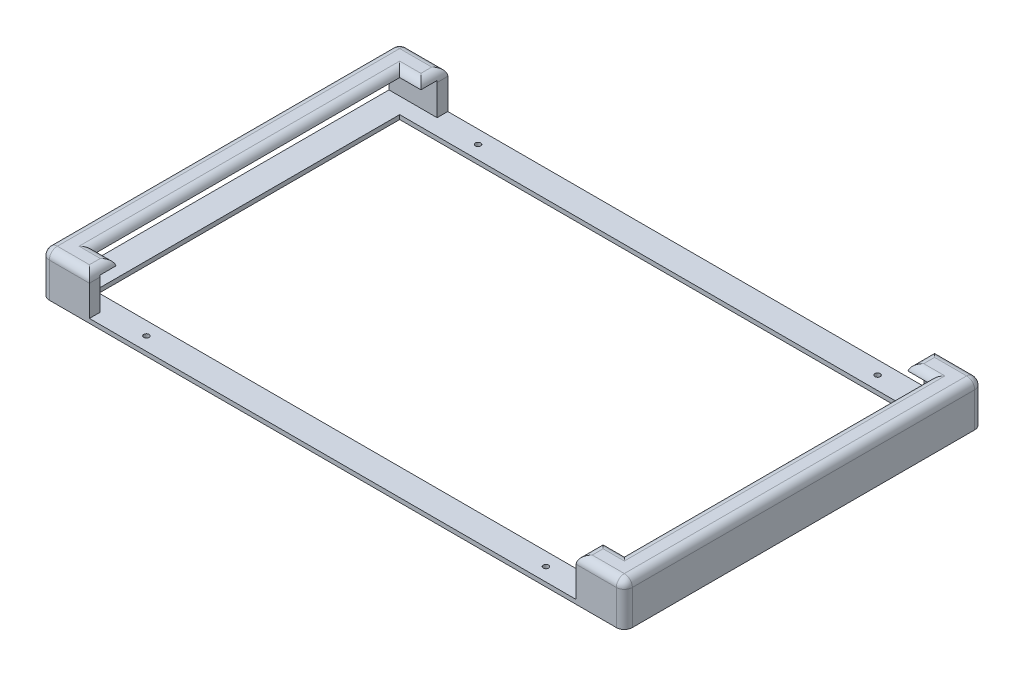
SolidWorks part; units mm, degrees
ref_plane "Спереди" through (0, 0, 0) normal (0, 0, 1) x (1, 0, 0)
ref_plane "Сверху" through (0, 0, 0) normal (0, 1, 0) x (1, 0, 0)
ref_plane "Справа" through (0, 0, 0) normal (1, 0, 0) x (0, 0, -1)
other "Configuration Table"
sketch "Основа" plane through (0, 0, 0) normal (0, 1, 0) x (1, 0, 0)
  line L1 (-109, -67) -> (109, -67)
  line L2 (-109, -67) -> (-109, 67)
  line L3 (-109, 67) -> (109, 67)
  line L4 (109, -67) -> (109, 67)
  line L5 (-109, -67) -> (109, 67) construction
  line L6 (-109, 67) -> (109, -67) construction
  line L7 (-99, -57) -> (99, -57)
  line L8 (-99, -57) -> (-99, 57)
  line L9 (-99, 57) -> (99, 57)
  line L10 (99, -57) -> (99, 57)
  line L11 (0, 57) -> (0, -57) construction
  line L12 (-99, 0) -> (99, 0) construction
  point P0 (0, 0)
  point P6 (0, 0)
  dimension "D1" = 134
  dimension "D2" = 218
  dimension "D3" = 114
  dimension "D4" = 198
extrude "Бобышка-Вытянуть2" add sketch "Основа" along normal blind 16
sketch "Эскиз2" plane through (-109, 0, 0) normal (-1, 0, 0) x (0, 0, 1)
  line L0 (0, 0) -> (0, 17.044) construction
  line L1 (63, 1.6) -> (-63, 1.6)
  line L2 (-63, 1.6) -> (-63, 13.6)
  line L3 (-63, 13.6) -> (63, 13.6)
  line L4 (-67, 0) -> (67, 0) construction
  line L5 (63, 1.6) -> (63, 13.6)
  point P10 (0, 13.6)
  point P11 (0, 1.6)
  dimension "D1" = 63
  dimension "D2" = 1.6
  dimension "D3" = 12
extrude "Вырез-Вытянуть1" cut sketch "Эскиз2" against normal blind 212
sketch "Эскиз3" plane through (0, 0, 67) normal (0, 0, 1) x (1, 0, 0)
  line L0 (0, 0) -> (0, 16) construction
  line L1 (-109, 16) -> (109, 16) construction
  line L2 (-109, 16) -> (-109, 0) construction
  line L3 (-91, 16) -> (91, 16)
  line L4 (-91, 16) -> (-91, 1.6)
  line L5 (-91, 1.6) -> (91, 1.6)
  line L6 (91, 16) -> (91, 1.6)
  line L7 (109, 16) -> (109, 0) construction
  line L8 (-109, 0) -> (109, 0) construction
  dimension "D1" = 18
  dimension "D2" = 18
  dimension "D3" = 1.6
extrude "Вырез-Вытянуть2" cut sketch "Эскиз3" against normal blind 134
sketch "Эскиз4" plane through (0, 1.6, 0) normal (0, 1, 0) x (1, 0, 0)
  line L0 (-91, 62) -> (91, 62) construction
  line L1 (-91, 67) -> (-91, 57) construction
  line L2 (91, 67) -> (91, 57) construction
  line L3 (-91, -62) -> (91, -62) construction
  line L4 (-91, -57) -> (-91, -67) construction
  line L5 (91, -57) -> (91, -67) construction
  line L6 (0, 67) -> (0, -65.4181) construction
  line L7 (-91, 67) -> (91, 67) construction
  line L8 (-74.6989, 67) -> (-74.6989, -67) construction
  line L9 (-91, -67) -> (91, -67) construction
  circle A0 centre (-74.6989, 62) radius 1
  circle A1 centre (-74.6989, -62) radius 1
  circle A2 centre (74.6989, -62) radius 1
  circle A3 centre (74.6989, 62) radius 1
extrude "Вырез-Вытянуть3" cut sketch "Эскиз4" against normal blind 1.6
fillet "Скругление1" radius 3 4 edges at (-109, 8, -67) (109, 8, -67) (109, 8, 67) (-109, 8, 67)
fillet "Скругление2" radius 3 10 edges at (-91, 16, -62) (-95, 16, -57) (-99, 16, 0) (-95, 16, 57) (-91, 16, 62) (-98.5, 16, 67) (-108.1213, 16, 66.1213) (-109, 16, 0) (-108.1213, 16, -66.1213) (-98.5, 16, -67)
fillet "Скругление3" radius 3 10 edges at (108.1213, 16, 66.1213) (98.5, 16, 67) (91, 16, 62) (95, 16, 57) (99, 16, 0) (95, 16, -57) (91, 16, -62) (98.5, 16, -67) (108.1213, 16, -66.1213) (109, 16, 0)
